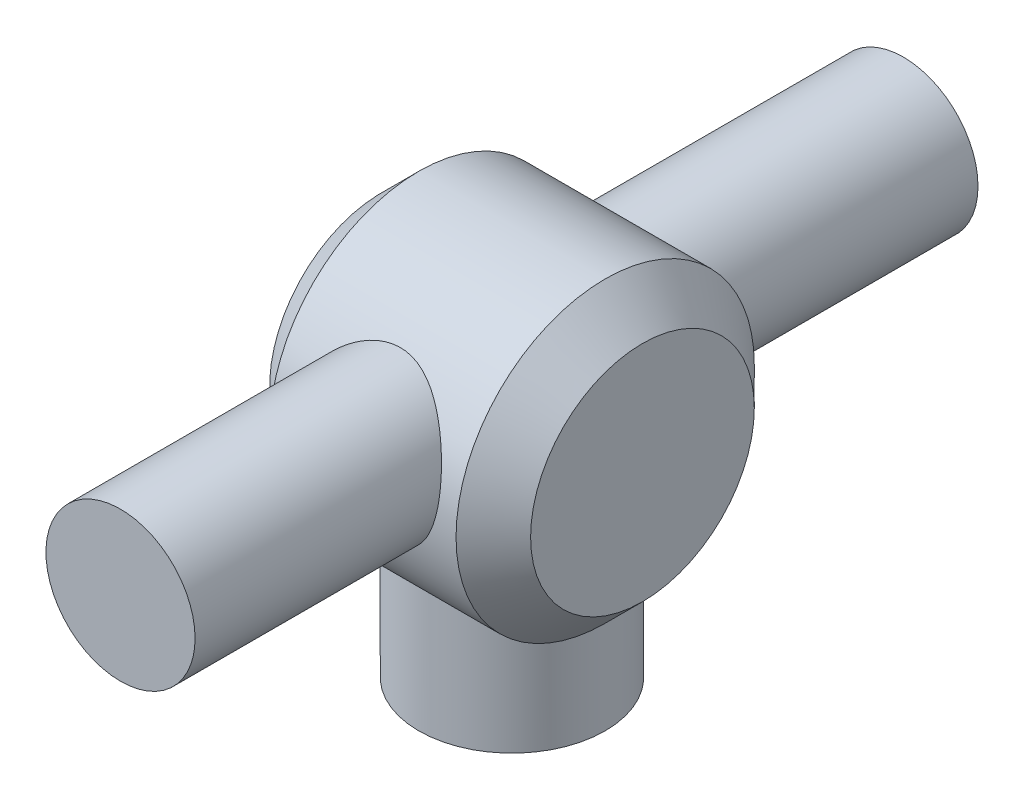
SolidWorks part; units mm, degrees
ref_plane "Front Plane" through (0, 0, 0) normal (0, 0, 1) x (1, 0, 0)
ref_plane "Top Plane" through (0, 0, 0) normal (0, 1, 0) x (1, 0, 0)
ref_plane "Right Plane" through (0, 0, 0) normal (1, 0, 0) x (0, 0, -1)
sketch "Sketch1" plane through (0, 0, 0) normal (0, 1, 0) x (1, 0, 0)
  circle A0 centre (0, 0) radius 5
  dimension "D1" = 10
extrude "Boss-Extrude1" add sketch "Sketch1" along normal blind 10
sketch "Sketch2" plane through (0, 0, 0) normal (1, 0, 0) x (0, 0, -1)
  circle A0 centre (0, 13) radius 8
  dimension "D2" = 16
  dimension "D1" = 13
extrude "Boss-Extrude2" add sketch "Sketch2" along normal mid plane 14
sketch "Sketch3" plane through (0, 0, 0) normal (0, 0, 1) x (1, 0, 0)
  line L0 (7, 21) -> (-7, 21) construction
  circle A0 centre (0, 14.305) radius 4
  dimension "D2" = 8
  dimension "D1" = 6.695
extrude "Boss-Extrude3" add sketch "Sketch3" along normal mid plane 42
chamfer "Chamfer1" distance 2 angle 45 2 edges at (-7, 13, -8) (7, 13, -8)
